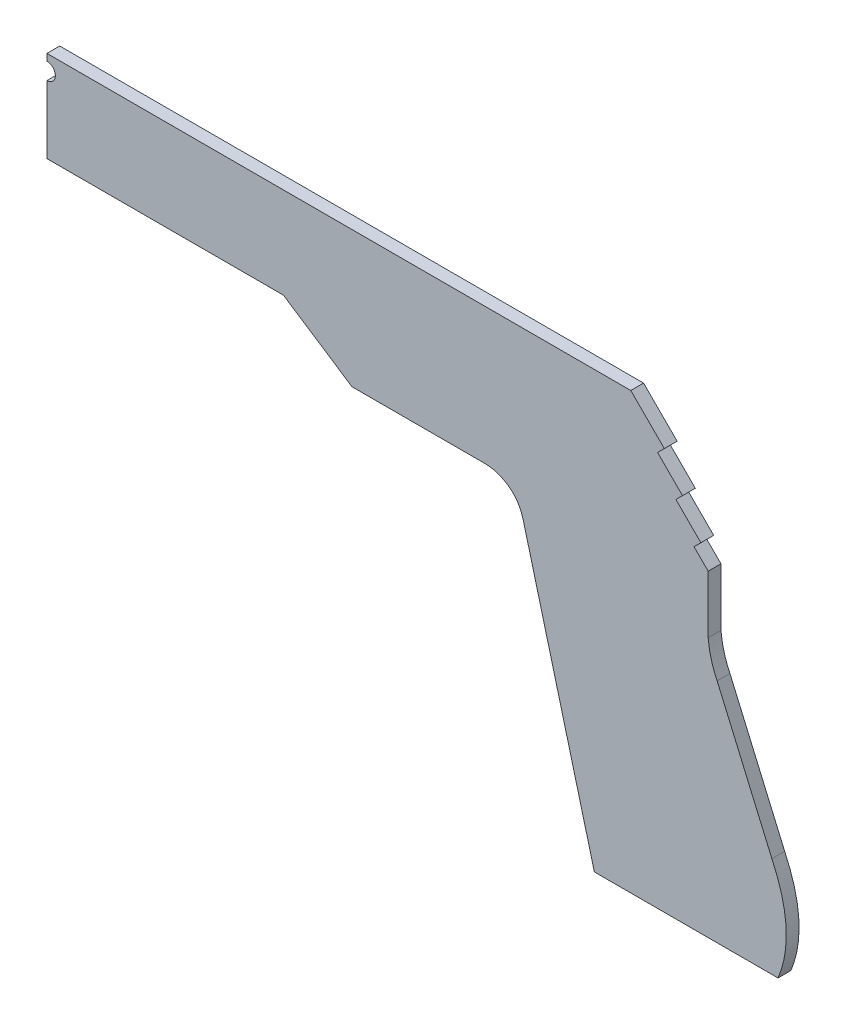
SolidWorks part; units mm, degrees
ref_plane "Front Plane" through (0, 0, 0) normal (0, 0, 1) x (1, 0, 0)
ref_plane "Top Plane" through (0, 0, 0) normal (0, 1, 0) x (1, 0, 0)
ref_plane "Right Plane" through (0, 0, 0) normal (1, 0, 0) x (0, 0, -1)
sketch "Sketch1" plane through (0, 0, 0) normal (0, 0, 1) x (1, 0, 0)
  line L0 (275.5001, 1169.5) -> (1377.5001, 1169.5) construction
  line L2 (-1087.7345, 1727.5042) -> (280.4846, 1727.5042)
  line L3 (280.4846, 1727.5042) -> (359.0895, 1648.8993)
  line L4 (359.0895, 1648.8993) -> (343.2885, 1633.0983)
  line L5 (343.2885, 1633.0983) -> (401.7169, 1574.6699)
  line L6 (401.7169, 1574.6699) -> (386.2482, 1559.2011)
  line L7 (386.2482, 1559.2011) -> (444.8176, 1500.6317)
  line L8 (444.8176, 1500.6317) -> (428.7287, 1484.5428)
  line L9 (428.7287, 1484.5428) -> (461.8502, 1451.4213)
  line L10 (461.8502, 1451.4213) -> (461.8502, 1316.4184)
  line L11 (482.9038, 1239.383) -> (611.1216, 942.6168)
  line L12 (625.5932, 707.6813) -> (195.1487, 707.6813)
  line L13 (195.1487, 707.6813) -> (28.627, 1338.0682)
  line L14 (-57.5535, 1408.3888) -> (-372.9542, 1408.3888)
  line L15 (-372.9542, 1408.3888) -> (-533.4481, 1513.9261)
  line L16 (-533.4481, 1513.9261) -> (-1087.7345, 1513.9261)
  line L17 (-1087.7345, 1513.9261) -> (-1087.7345, 1672.3872)
  line L18 (-1087.7345, 1711.784) -> (-1087.7345, 1727.5042)
  arc A0 (-1087.7345, 1672.3872) -> (-1087.7345, 1711.784) centre (-1087.7345, 1692.0856) ccw
  spline S0 degree 2 poles (461.8502, 1316.4184) (465.3906, 1273.8387) (484.0713, 1237.0481) knots 0 0 0 1 1 1
  spline S1 degree 2 poles (611.1216, 942.6168) (670.4005, 816.5965) (625.5932, 707.6813) knots 0 0 0 1 1 1
  spline S2 degree 2 poles (28.627, 1338.0682) (19.1318, 1374.5434) (-9.423, 1392.5705) knots 0 0 0 1 1 1
  spline S3 degree 2 poles (-9.423, 1392.5705) (-32.2182, 1407.2497) (-57.5535, 1408.3888) knots 0 0 0 1 1 1
extrude "Boss-Extrude2" add sketch "Sketch1" along normal blind 30 contours S3 S2 L13 L12 S1 L11 S0 L10 L9 L8 L7 L6 L5 L4 L3 L2 L18 A0 L17 L16 L15 L14 region at (-403.625, 1707.3995, 0)
